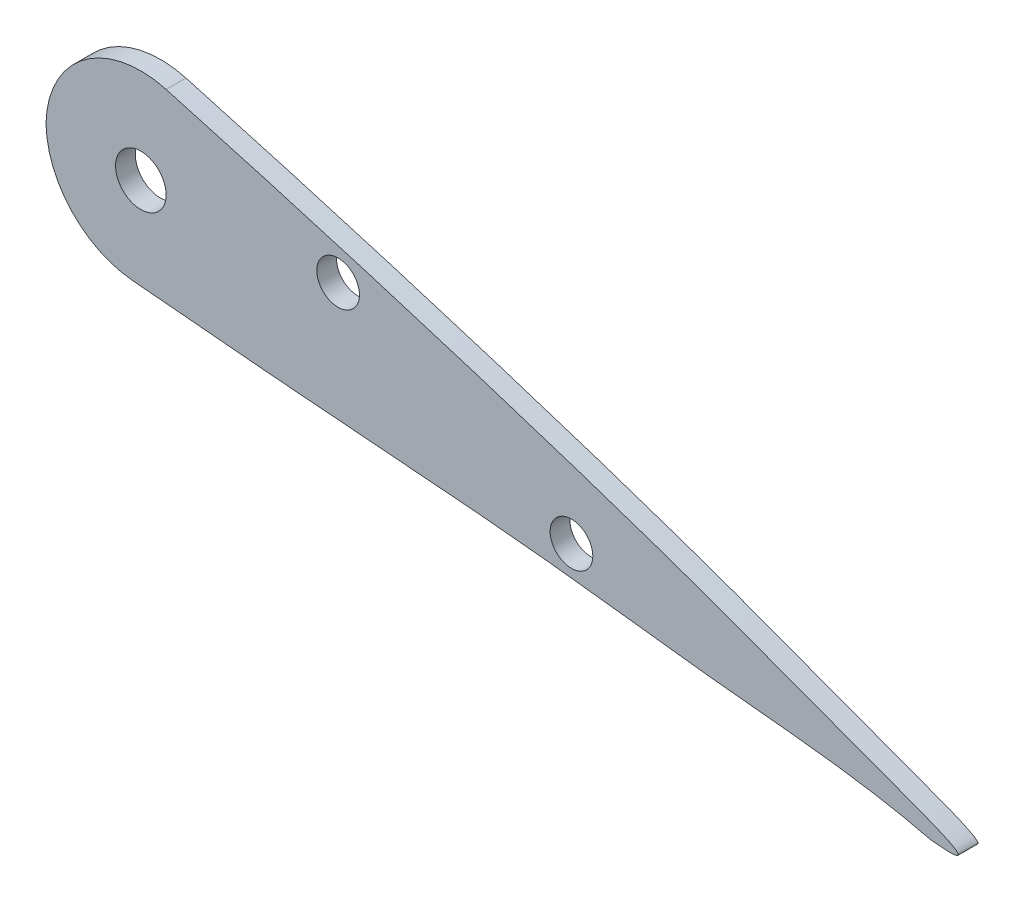
SolidWorks part; units mm, degrees
material "Balsa"
ref_plane "Front Plane" through (0, 0, 0) normal (0, 0, 1) x (1, 0, 0)
ref_plane "Top Plane" through (0, 0, 0) normal (0, 1, 0) x (1, 0, 0)
ref_plane "Right Plane" through (0, 0, 0) normal (1, 0, 0) x (0, 0, -1)
sketch "Sketch1" plane through (0, 0, 0) normal (0, 0, 1) x (1, 0, 0)
  spline S0 degree 3 poles (0.0006, 0.0001) (0.8106, 7.3592) (8.6491, 17.8566) (26.2867, 29.9752) (52.1111, 42.0692) (89.5976, 49.2908) (131.4008, 47.8848) (173.2567, 40.0411) (217.9611, 29.613) (256.9521, 19.5289) (290.3598, 8.711) (301.2732, 4.3828) (314.8169, -0.5162) (309.8463, 0.0001) knots 0 0 0 0 0.060864 0.113688 0.188609 0.312909 0.448482 0.557612 0.691544 0.852438 0.929756 0.976058 1 1 1 1
  spline S1 degree 3 poles (309.8463, 0.0001) (303.9568, 1.471) (293.9895, 2.094) (276.264, 4.5144) (260.8463, 5.4274) (235.8588, 7.8703) (205.1014, 8.8381) (157.7186, 9.0307) (110.4973, 6.1815) (66.5062, -0.5867) (36.4547, -6.0985) (15.3166, -6.1891) (1.2307, -6.9241) (0.0006, 0.0001) knots 0 0 0 0 0.057787 0.095275 0.171021 0.205339 0.335319 0.464904 0.658702 0.785512 0.893517 0.943092 1 1 1 1
extrude "Boss-Extrude1" add sketch "Sketch1" along normal blind 1.5875
sketch "Sketch2" plane through (0, 0, 1.5875) normal (0, 0, 1) x (1, 0, 0)
  circle A0 centre (20.32, 10.16) radius 6.35
  circle A1 centre (227.2963, 19.0501) radius 3.175
  dimension "D2" = 12.7
  dimension "D3" = 6.35
  dimension "D6" = 20.32
  dimension "D1" = 82.55
  dimension "D4" = 19.05
  dimension "D5" = 10.16
extrude "Cut-Extrude1" cut sketch "Sketch2" against normal through all
sketch "Sketch3" plane through (0, 0, 1.5875) normal (0, 0, 1) x (1, 0, 0)
  line L11 (-90.3395, -69.7561) -> (238.7263, -69.7561)
  line L12 (-90.3395, -69.7561) -> (-90.3395, 107.5465)
  line L13 (-90.3395, 107.5465) -> (238.7263, 107.5465)
  line L14 (238.7263, -69.7561) -> (238.7263, 107.5465)
  circle A1 centre (227.2963, 19.0501) radius 3.175 construction
  dimension "D1" = 11.43
extrude "Cut-Extrude2" cut sketch "Sketch3" against normal through all contours L14 L13 L12 L11
fillet "Fillet1" radius 7.62 2 edges at (238.7263, 7.3795, 0.7937) (238.7263, 24.1211, 0.7937)
sketch "Sketch4" plane through (0, 0, 1.5875) normal (0, 0, 1) x (1, 0, 0)
  circle A0 centre (246.3463, 14.163) radius 2.032
  dimension "D1" = 4.064
  dimension "D2" = 63.5
  dimension "D3" = 14.1628
extrude "Cut-Extrude3" cut sketch "Sketch4" against normal blind 2.54
sketch "Sketch5" plane through (0, 0, 1.5875) normal (0, 0, 1) x (1, 0, 0)
  circle A0 centre (262.1963, 14.9701) radius 1.7145
  circle A1 centre (280.9442, 6.1769) radius 1.7145
  point P4 (262.1963, 14.9701)
  point P5 (288.9633, 6.8958)
  point P6 (280.9442, 6.1769)
  dimension "D1" = 3.429
extrude "Cut-Extrude4" cut sketch "Sketch5" against normal blind 2.54
equation "\"D1@Sketch3\"=0.25+0.2"
